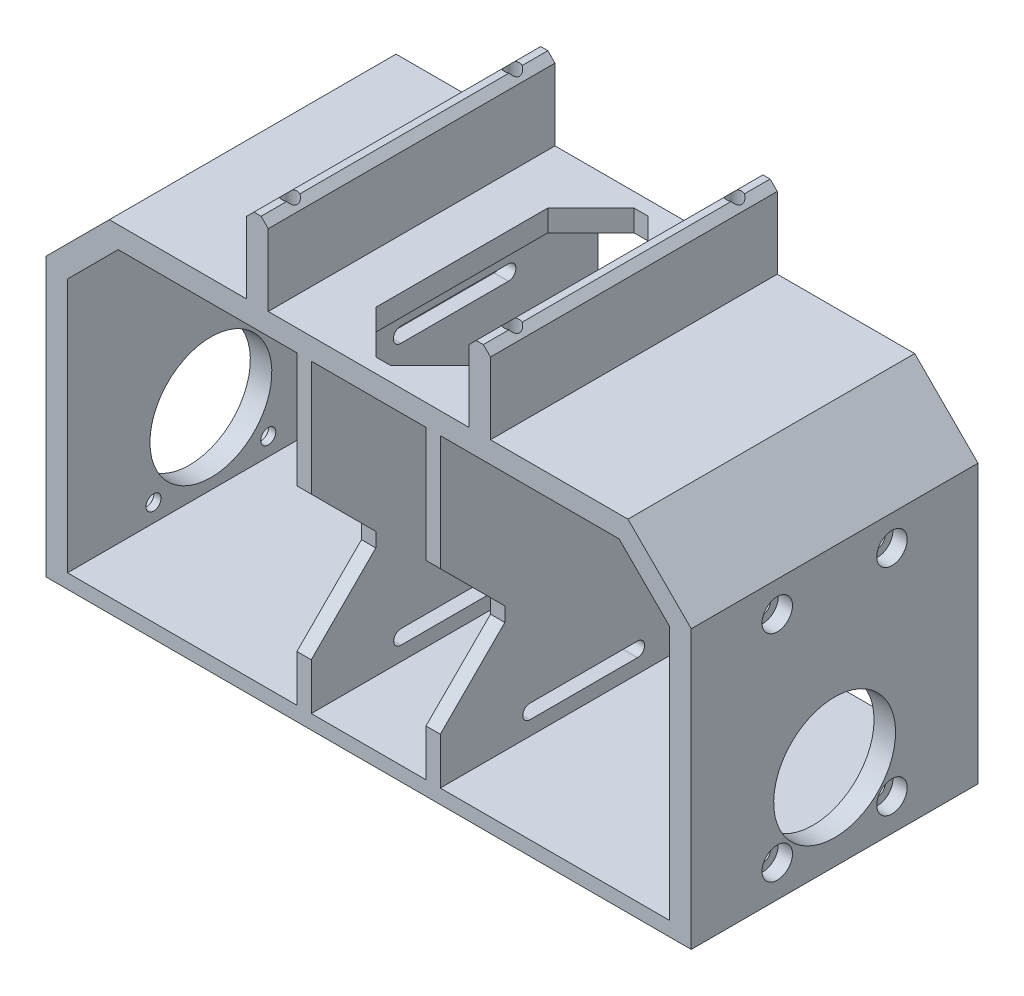
SolidWorks part; units mm, degrees
ref_plane "Front Plane" through (0, 0, 0) normal (0, 0, 1) x (1, 0, 0)
ref_plane "Top Plane" through (0, 0, 0) normal (0, 1, 0) x (1, 0, 0)
ref_plane "Right Plane" through (0, 0, 0) normal (1, 0, 0) x (0, 0, -1)
sketch "Sketch3" plane through (0, 0, 0) normal (0, 0, 1) x (1, 0, 0)
  line L0 (0, -1093.1981) -> (0, 53566.7066) construction
  line L1 (-42, 0) -> (-42, 35)
  line L2 (-42, 35) -> (-34.9289, 42.0711)
  line L3 (-34.9289, 42.0711) -> (34.9289, 42.0711)
  line L4 (34.9289, 42.0711) -> (42, 35)
  line L5 (42, 35) -> (42, 0)
  line L6 (-45, 0) -> (-45, 36.2426)
  line L7 (-45, 36.2426) -> (-36.1716, 45.0711)
  line L8 (-36.1716, 45.0711) -> (36.1716, 45.0711)
  line L9 (36.1716, 45.0711) -> (45, 36.2426)
  line L10 (45, 36.2426) -> (45, 0)
  line L13 (-45, 0) -> (-45, -2.5)
  line L14 (-45, -2.5) -> (45, -2.5)
  line L15 (45, -2.5) -> (45, 0)
  line L17 (-42, 0) -> (-42, -0.5)
  line L18 (-42, -0.5) -> (42, -0.5)
  line L19 (42, -0.5) -> (42, 0)
  dimension "D1" = 35
  dimension "D2" = 42
  dimension "D3" = 10
  dimension "D5" = 2
  dimension "D6" = 0.5
  dimension "D4" = 3
extrude "Boss-Extrude3" add sketch "Sketch3" along normal blind 20 and the other way blind 20
sketch "Sketch4" plane through (-45, 0, 0) normal (-1, 0, 0) x (0, 0, 1)
  line L0 (-1023.7692, 0) -> (48976.2308, 0) construction
  circle A0 centre (0, 9.5) radius 8.5
  dimension "D1" = 17
  dimension "D2" = 9.5
extrude "Cut-Extrude1" cut sketch "Sketch4" against normal through all
sketch "Sketch5" plane through (-45, 0, 0) normal (-1, 0, 0) x (0, 0, 1)
  line L0 (-1000, 0) -> (49000, 0) construction
  line L1 (-8, 32) -> (8, 32) construction
  line L2 (-8, 32) -> (-8, 2) construction
  line L3 (-8, 2) -> (8, 2) construction
  line L4 (8, 32) -> (8, 2) construction
  line L5 (-8, 32) -> (8, 2) construction
  line L6 (-8, 2) -> (8, 32) construction
  circle A0 centre (-8, 32) radius 1.05
  circle A1 centre (8, 32) radius 1.05
  circle A2 centre (8, 2) radius 1.05
  circle A3 centre (-8, 2) radius 1.05
  point P0 (0, 17)
  dimension "D3" = 2.1
  dimension "D1" = 16
  dimension "D2" = 30
  dimension "D4" = 17
extrude "Cut-Extrude2" cut sketch "Sketch5" against normal through all
sketch "Sketch6" plane through (0, 0, 0) normal (0, 0, 1) x (1, 0, 0)
  line L0 (34.9289, 42.0711) -> (-34.9289, 42.0711) construction
  line L1 (-8, -0.5) -> (-10, -0.5)
  line L2 (-8, -0.5) -> (-8, 42.0711)
  line L3 (-8, 42.0711) -> (-10, 42.0711)
  line L4 (-10, -0.5) -> (-10, 42.0711)
  line L5 (-8, -0.5) -> (-10, 42.0711) construction
  line L6 (-8, 42.0711) -> (-10, -0.5) construction
  line L7 (-42, -0.5) -> (42, -0.5) construction
  line L8 (0, -1000) -> (0, 49000) construction
  line L13 (8, 42.0711) -> (10, -0.5) construction
  line L14 (8, -0.5) -> (10, 42.0711) construction
  line L15 (10, -0.5) -> (10, 42.0711)
  line L16 (8, 42.0711) -> (10, 42.0711)
  line L17 (8, -0.5) -> (8, 42.0711)
  line L18 (8, -0.5) -> (10, -0.5)
  point P0 (0, 212.3553)
  point P15 (-9, 20.7855)
  point P17 (9, 20.7855)
  dimension "D1" = 2
  dimension "D2" = 8
extrude "Boss-Extrude4" add sketch "Sketch6" along normal up to surface (20 mm away) and the other way up to surface (20 mm away) up to face at (0, 26.2712, 20) other way up to face at (0, 25.5237, -20)
sketch "Sketch7" plane through (-10, 0, 0) normal (-1, 0, 0) x (0, 0, 1)
  line L0 (0, -1000) -> (0, 49000) construction
  line L1 (-20, 26) -> (-20, 6)
  line L2 (-20, 6) -> (-11, 15)
  line L3 (-11, 15) -> (-11, 17)
  line L4 (-11, 17) -> (-20, 26)
  line L5 (-20, 36.2426) -> (-20, -2.5) construction
  point P9 (-20, 16)
  dimension "D1" = 45
  dimension "D2" = 9
  dimension "D3" = 16
  dimension "D4" = 20
extrude "Cut-Extrude4" cut sketch "Sketch7" against normal up to surface (20 mm away) up to face at (10, 20.7855, 0)
mirror "Mirror1" about plane through (0, 0, 0) normal (0, 0, 1) of "Cut-Extrude4"
sketch "Sketch8" plane through (-45, 0, 0) normal (-1, 0, 0) x (0, 0, 1)
  circle A0 centre (-8, 32) radius 2.125
  circle A1 centre (8, 32) radius 2.125
  circle A2 centre (8, 2) radius 2.125
  circle A3 centre (-8, 2) radius 2.125
  dimension "D1" = 4.25
extrude "Cut-Extrude5" cut sketch "Sketch8" against normal blind 2
mirror "Mirror2" about plane through (0, 0, 0) normal (1, 0, 0) of "Cut-Extrude5"
sketch "Sketch9" plane through (0, 0, 20) normal (0, 0, 1) x (1, 0, 0)
  line L0 (14, 55.0711) -> (17, 55.0711) construction
  line L2 (17, 55.0711) -> (16, 56.0711)
  line L3 (16, 56.0711) -> (15, 56.0711)
  line L4 (15, 56.0711) -> (14, 55.0711)
  line L5 (14, 55.0711) -> (14, 45.0711)
  line L6 (36.1716, 45.0711) -> (-36.1716, 45.0711) construction
  line L7 (14, 45.0711) -> (17, 45.0711)
  line L8 (17, 45.0711) -> (17, 55.0711)
  dimension "D1" = 14
  dimension "D2" = 3
  dimension "D3" = 45
  dimension "D4" = 1
  dimension "D5" = 10
extrude "Boss-Extrude5" add sketch "Sketch9" against normal up to surface (40 mm away) up to face at (0, 20.3376, -20)
mirror "Mirror3" about plane through (0, 0, 0) normal (1, 0, 0) of "Boss-Extrude5"
sketch "Sketch10" plane through (0, 56.0711, 0) normal (0, 1, 0) x (1, 0, 0)
  line L1 (15.5, -15.5) -> (-15.5, -15.5) construction
  line L2 (15.5, -15.5) -> (15.5, 15.5) construction
  line L3 (15.5, 15.5) -> (-15.5, 15.5) construction
  line L4 (-15.5, -15.5) -> (-15.5, 15.5) construction
  line L5 (15.5, -15.5) -> (-15.5, 15.5) construction
  line L6 (15.5, 15.5) -> (-15.5, -15.5) construction
  circle A0 centre (-15.5, 15.5) radius 1.05
  circle A1 centre (15.5, 15.5) radius 1.05
  circle A2 centre (15.5, -15.5) radius 1.05
  circle A3 centre (-15.5, -15.5) radius 1.05
  point P0 (0, 0)
  dimension "D2" = 2.1
  dimension "D1" = 31
extrude "Cut-Extrude6" cut sketch "Sketch10" against normal blind 10
sketch "Sketch11" plane through (-10, 0, 0) normal (-1, 0, 0) x (0, 0, 1)
  line L0 (-7.5, 39.0211) -> (7.5, 39.0211) construction
  line L1 (-7.5, 40.0711) -> (7.5, 40.0711)
  line L2 (-7.5, 37.9711) -> (7.5, 37.9711)
  line L3 (20, 42.0711) -> (-20, 42.0711) construction
  line L4 (-7.5, 2.5) -> (7.5, 2.5) construction
  line L5 (-7.5, 3.5) -> (7.5, 3.5)
  line L6 (-7.5, 1.5) -> (7.5, 1.5)
  line L7 (20, -0.5) -> (-20, -0.5) construction
  arc A0 (-7.5, 40.0711) -> (-7.5, 37.9711) centre (-7.5, 39.0211) ccw
  arc A1 (7.5, 37.9711) -> (7.5, 40.0711) centre (7.5, 39.0211) ccw
  arc A2 (-7.5, 3.5) -> (-7.5, 1.5) centre (-7.5, 2.5) ccw
  arc A3 (7.5, 1.5) -> (7.5, 3.5) centre (7.5, 2.5) ccw
  point P2 (0, 39.0211)
  point P7 (0, 2.5)
  point P17 (0, 0)
  dimension "D1" = 2.1
  dimension "D2" = 2
  dimension "D3" = 15
  dimension "D4" = 2
  dimension "D5" = 2
extrude "Cut-Extrude7" cut sketch "Sketch11" against normal up to surface (20 mm away) up to face at (10, 17.5952, 0)
sketch "Sketch12" plane through (0, 45.0711, 0) normal (0, 1, 0) x (1, 0, 0)
  line L0 (-7, 12) -> (-7, -12)
  line L1 (-7, -12) -> (-1, -18)
  line L2 (-1, -18) -> (1, -18)
  line L3 (1, -18) -> (7, -12)
  line L4 (7, -12) -> (7, 12)
  line L5 (7, 12) -> (1, 18)
  line L6 (1, 18) -> (-1, 18)
  line L7 (-1, 18) -> (-7, 12)
  line L8 (-7, -12) -> (7, 12) construction
  line L9 (-7, 12) -> (7, -12) construction
  line L10 (-7, 12) -> (7, 12) construction
  line L11 (-7, -12) -> (7, -12) construction
  line L12 (-8, -20) -> (-8, 20) construction
  line L13 (14, -20) -> (-14, -20) construction
  point P2 (0, 0)
  point P9 (0, 0)
  point P10 (0, 0)
  point P11 (0, 0)
  point P12 (0.7772, -14.472)
  point P16 (1.528, 14.472)
  point P17 (1.4221, 12.5779)
  dimension "D1" = 45
  dimension "D2" = 24
  dimension "D3" = 1
  dimension "D4" = 2
extrude "Cut-Extrude8" cut sketch "Sketch12" against normal up to surface (3 mm away) up to face at (0, 42.0711, 0)
